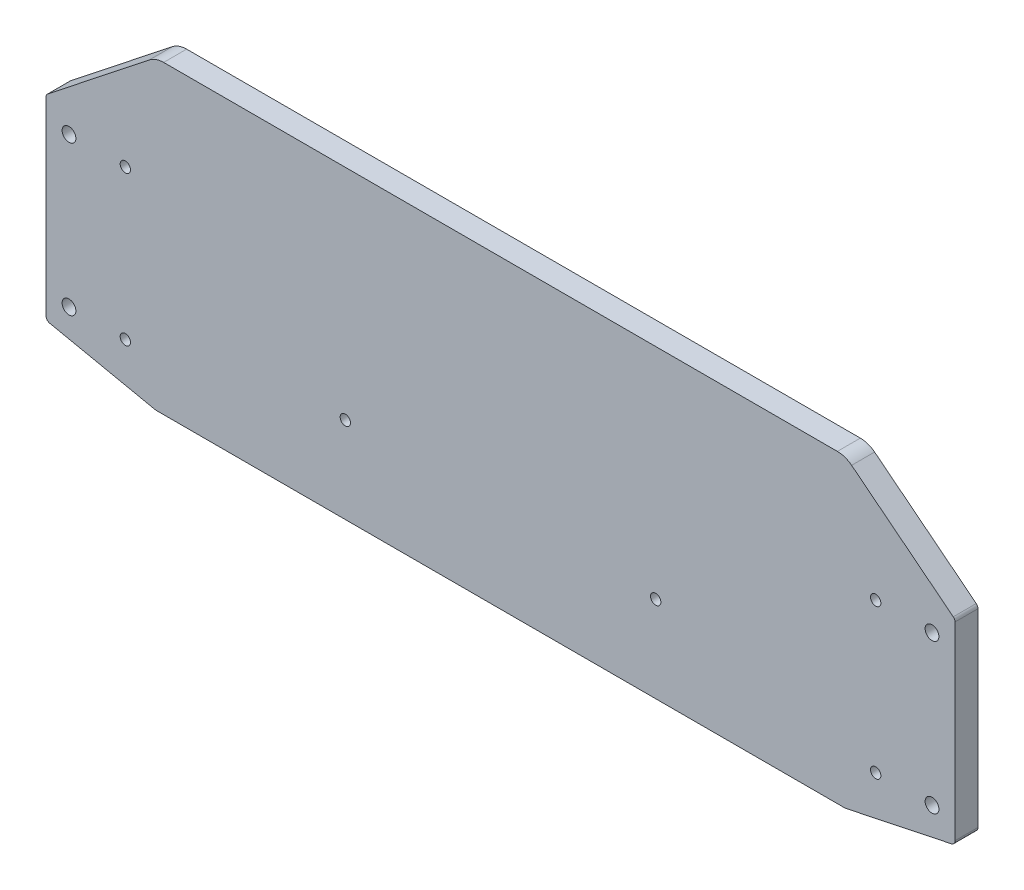
SolidWorks part; units mm, degrees
ref_plane "Plan de face" through (0, 0, 0) normal (0, 0, 1) x (1, 0, 0)
ref_plane "Plan de dessus" through (0, 0, 0) normal (0, 1, 0) x (1, 0, 0)
ref_plane "Plan de droite" through (0, 0, 0) normal (1, 0, 0) x (0, 0, -1)
sketch "Esquisse1" plane through (0, 0, 0) normal (0, 0, 1) x (1, 0, 0)
  line L0 (-197.7, 42.5) -> (-150, 80.2)
  line L1 (-197.7, 42.5) -> (197.7, 42.5)
  line L2 (-197.7, 42.5) -> (-197.7, -42.5)
  line L3 (-197.7, -42.5) -> (197.7, -42.5)
  line L4 (197.7, 42.5) -> (197.7, -42.5)
  line L5 (-150, 80.2) -> (150, 80.2)
  line L6 (-150, 80.2) -> (-150, 42.5)
  line L7 (-150, 42.5) -> (150, 42.5)
  line L8 (150, 80.2) -> (150, 42.5)
  line L9 (-150, -42.5) -> (150, -42.5)
  line L10 (-150, -42.5) -> (-150, -52.5)
  line L11 (-150, -52.5) -> (150, -52.5)
  line L12 (150, -42.5) -> (150, -52.5)
  line L13 (150, 80.2) -> (197.7, 42.5)
  line L14 (197.7, -42.5) -> (150, -52.5)
  line L15 (-150, -52.5) -> (-197.7, -42.5)
  dimension "D1" = 85
  dimension "D2" = 395.4
  dimension "D3" = 300
  dimension "D4" = 300
  dimension "D5" = 47.7
  dimension "D6" = 47.7
  dimension "D7" = 10
  dimension "D8" = 37.7
  dimension "D9" = 150
  dimension "D10" = 42.5
extrude "Boss.-Extru.1" add sketch "Esquisse1" along normal blind 10 contours L4 L1 L2 L3 | L8 L5 L6 L1 | L6 L0 L1 | L12 L3 L10 L11 | L15 L10 L3 | L13 L8 L1 | L14 L3 L12 region at (-165.9, 55.0667, 0) region at (0, 0, 0) region at (0, 61.35, 0) region at (-165.9, -45.8333, 0) region at (165.9, 55.0667, 0) region at (0, -47.5, 0) region at (165.9, -45.8333, 0)
sketch "Esquisse2" plane through (0, 0, 10) normal (0, 0, 1) x (1, 0, 0)
  line L1 (-197.7, 22.5) -> (-177.7, 22.5)
  line L2 (-197.7, 22.5) -> (-197.7, 42.5)
  line L3 (-197.7, 42.5) -> (-177.7, 42.5)
  line L4 (-177.7, 22.5) -> (-177.7, 42.5)
  line L5 (177.7, 22.5) -> (197.7, 22.5)
  line L6 (177.7, 22.5) -> (177.7, 42.5)
  line L7 (177.7, 42.5) -> (197.7, 42.5)
  line L8 (197.7, 22.5) -> (197.7, 42.5)
  line L9 (177.7, -22.5) -> (197.7, -22.5)
  line L10 (177.7, -22.5) -> (177.7, -42.5)
  line L11 (177.7, -42.5) -> (197.7, -42.5)
  line L12 (197.7, -22.5) -> (197.7, -42.5)
  line L13 (-197.7, -22.5) -> (-177.7, -22.5)
  line L14 (-197.7, -22.5) -> (-197.7, -42.5)
  line L15 (-197.7, -42.5) -> (-177.7, -42.5)
  line L16 (-177.7, -22.5) -> (-177.7, -42.5)
  line L17 (197.7, 42.5) -> (197.7, -42.5) construction
  line L18 (-197.7, 42.5) -> (-197.7, -42.5) construction
  dimension "D1" = 20
  dimension "D2" = 20
  dimension "D3" = 20
  dimension "D4" = 20
  dimension "D5" = 20
  dimension "D6" = 20
  dimension "D7" = 20
  dimension "D8" = 20
  dimension "D9" = 20
  dimension "D10" = 20
  dimension "D11" = 20
  dimension "D12" = 20
  dimension "D13" = 0
  dimension "D14" = 0
  dimension "D15" = 0
  dimension "D16" = 0
sketch "Esquisse3" plane through (0, 0, 10) normal (0, 0, 1) x (1, 0, 0)
  line L0 (-197.7, 42.5) -> (-177.7, 42.5) construction
  line L2 (-177.7, 22.5) -> (-177.7, 42.5) construction
  line L4 (-197.7, -22.5) -> (-177.7, -22.5) construction
  line L5 (-177.7, -22.5) -> (-177.7, -42.5) construction
  line L8 (177.7, -22.5) -> (197.7, -22.5) construction
  line L9 (177.7, -22.5) -> (177.7, -42.5) construction
  line L12 (177.7, 22.5) -> (177.7, 42.5) construction
  line L13 (177.7, 42.5) -> (197.7, 42.5) construction
  circle A0 centre (-163.2, 32.5) radius 2.25
  circle A1 centre (-187.7, 32.5) radius 3
  circle A2 centre (-187.7, 57) radius 2.25
  circle A3 centre (-187.7, -32.5) radius 3
  circle A4 centre (-163.2, -32.5) radius 2.25
  circle A6 centre (187.7, -32.5) radius 3
  circle A7 centre (163.2, -32.5) radius 2.25
  circle A9 centre (187.7, 32.5) radius 3
  circle A10 centre (163.2, 32.5) radius 2.25
  dimension "D1" = 6
  dimension "D5" = 4.5
  dimension "D6" = 4.5
  dimension "D10" = 6
  dimension "D13" = 4.5
  dimension "D14" = 14.5
  dimension "D17" = 14.5
  dimension "D19" = 6
  dimension "D27" = 4.5
  dimension "D28" = 4.5
  dimension "D30" = 6
  dimension "D15" = 14.5
  dimension "D7" = 14.5
  dimension "D2" = 10
  dimension "D3" = 10
  dimension "D4" = 10
  dimension "D8" = 14.5
  dimension "D9" = 10
  dimension "D11" = 10
  dimension "D12" = 10
  dimension "D16" = 10
  dimension "D20" = 10
  dimension "D21" = 10
  dimension "D26" = 10
  dimension "D31" = 10
  dimension "D32" = 10
  dimension "D33" = 10
extrude "Enlèv. mat.-Extru.1" cut sketch "Esquisse3" against normal blind 10
sketch "Esquisse4" plane through (0, 0, 10) normal (0, 0, 1) x (1, 0, 0)
  line L0 (-197.7, 42.5) -> (-197.7, -42.5) construction
  line L1 (-150, -52.5) -> (150, -52.5) construction
  line L2 (197.7, 42.5) -> (197.7, -42.5) construction
  circle A0 centre (-67.5, -15) radius 2.25
  circle A1 centre (67.5, -15) radius 2.25
  dimension "D1" = 4.5
  dimension "D2" = 4.5
  dimension "D3" = 130.2
  dimension "D4" = 37.5
  dimension "D5" = 37.5
  dimension "D6" = 130.2
extrude "Enlèv. mat.-Extru.2" cut sketch "Esquisse4" against normal blind 10
fillet "Congé1" radius 10 4 edges at (-150, 80.2, 5) (150, 80.2, 5) (150, -52.5, 5) (-150, -52.5, 5)
fillet "Congé2" radius 2 4 edges at (-197.7, -42.5, 5) (-197.7, 42.5, 5) (197.7, -42.5, 5) (197.7, 42.5, 5)
